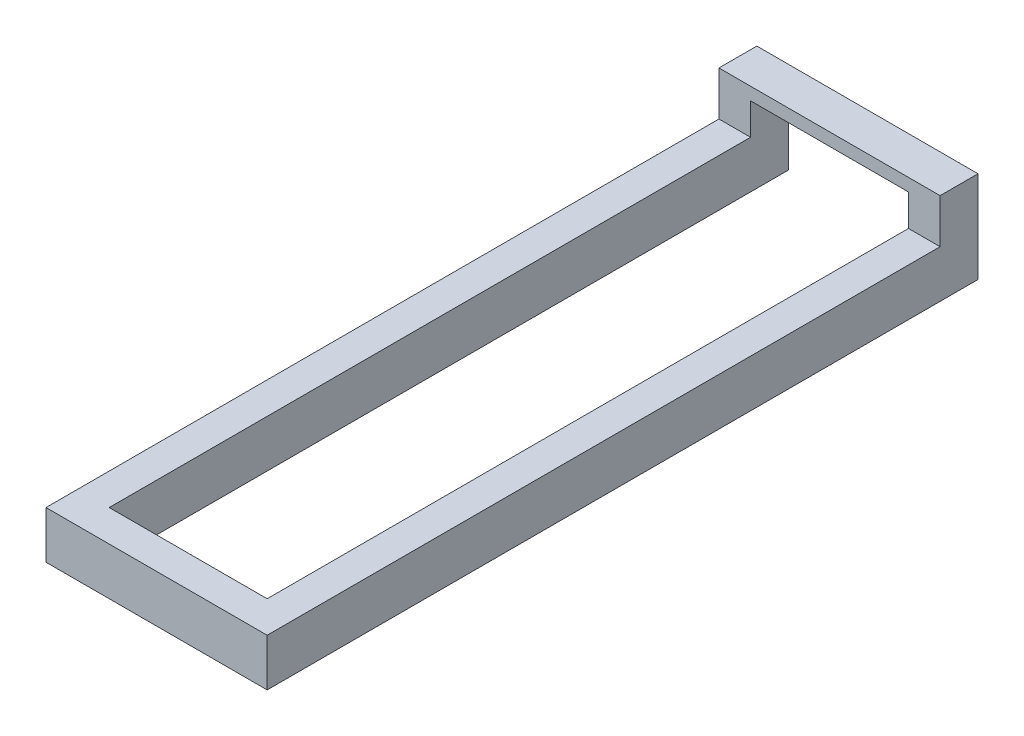
SolidWorks part; units mm, degrees
ref_plane "Front Plane" through (0, 0, 0) normal (0, 0, 1) x (1, 0, 0)
ref_plane "Top Plane" through (0, 0, 0) normal (0, 1, 0) x (1, 0, 0)
ref_plane "Right Plane" through (0, 0, 0) normal (1, 0, 0) x (0, 0, -1)
sketch "Sketch1" plane through (0, 0, 0) normal (0, 1, 0) x (1, 0, 0)
  line L0 (25, 107.5) -> (35, 107.5)
  line L2 (-25, 107.5) -> (-25, -107.5)
  line L3 (-25, -107.5) -> (25, -107.5)
  line L4 (25, 107.5) -> (25, -107.5)
  line L5 (-25, 107.5) -> (25, -107.5) construction
  line L6 (-25, -107.5) -> (25, 107.5) construction
  line L7 (35, 107.5) -> (35, -117.5)
  line L8 (35, -117.5) -> (-35, -117.5)
  line L9 (-35, -117.5) -> (-35, 107.5)
  line L10 (-35, 107.5) -> (-25, 107.5)
  point P0 (0, 0)
  dimension "D1" = 50
  dimension "D2" = 215
  dimension "D3" = 50
  dimension "D4" = 10
  dimension "D5" = 10
  dimension "D6" = 10
extrude "Boss-Extrude1" add sketch "Sketch1" along normal mid plane 15
sketch "Sketch2" plane through (0, 0, -107.5) normal (0, 0, -1) x (-1, 0, 0)
  line L1 (-35, 7.5) -> (-25, 7.5)
  line L2 (-35, 7.5) -> (-35, 17.5)
  line L3 (-35, 17.5) -> (-25, 17.5)
  line L4 (-25, 7.5) -> (-25, 17.5)
  line L5 (25, 7.5) -> (35, 7.5)
  line L6 (25, 7.5) -> (25, 17.5)
  line L7 (25, 17.5) -> (35, 17.5)
  line L8 (35, 7.5) -> (35, 17.5)
  line L9 (-35, 17.5) -> (35, 17.5)
  line L10 (-35, 17.5) -> (-35, 21.5)
  line L11 (-35, 21.5) -> (35, 21.5)
  line L12 (35, 17.5) -> (35, 21.5)
  line M7 (-25, 7.5) -> (-35, 7.5)
  dimension "D1" = 10
  dimension "D2" = 4
  dimension "D3" = 70
  dimension "D4" = 10
extrude "Boss-Extrude2" add sketch "Sketch2" against normal blind 12 contours L4 L3 L2 M7 | L7 L12 L11 L10 L3 L9 | L5 L8 L7 L6 region at (30, 12.5, -107.5) region at (0, 19.5, -107.5) region at (-30, 12.5, -107.5)
